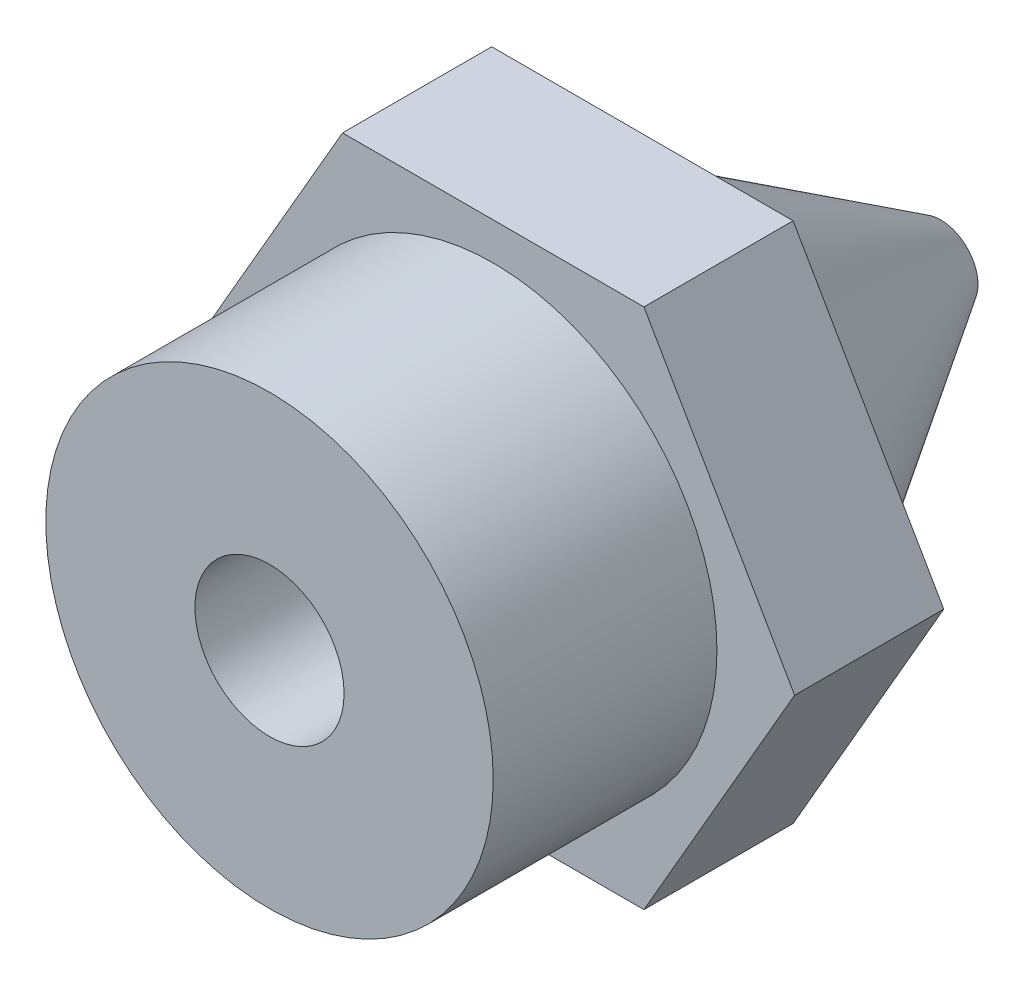
SolidWorks part; units mm, degrees
ref_plane "Plan de face" through (0, 0, 0) normal (0, 0, 1) x (1, 0, 0)
ref_plane "Plan de dessus" through (0, 0, 0) normal (0, 1, 0) x (1, 0, 0)
ref_plane "Plan de droite" through (0, 0, 0) normal (1, 0, 0) x (0, 0, -1)
sketch "Esquisse1" plane through (0, 0, 0) normal (0, 0, 1) x (1, 0, 0)
  line L1 (4.0415, 0) -> (2.0207, 3.5)
  line L2 (2.0207, 3.5) -> (-2.0207, 3.5)
  line L3 (-2.0207, 3.5) -> (-4.0415, 0)
  line L4 (-4.0415, 0) -> (-2.0207, -3.5)
  line L5 (-2.0207, -3.5) -> (2.0207, -3.5)
  line L6 (2.0207, -3.5) -> (4.0415, 0)
  circle A0 centre (0, 0) radius 3.5 construction
  dimension "D1" = 7
extrude "Boss.-Extru.1" add sketch "Esquisse1" along normal blind 9
sketch "Esquisse2" plane through (0, 0, 9) normal (0, 0, 1) x (1, 0, 0)
  line L1 (-7.9912, 5.5023) -> (7.566, 5.5023)
  line L2 (-7.9912, 5.5023) -> (-7.9912, -5.9665)
  line L3 (-7.9912, -5.9665) -> (7.566, -5.9665)
  line L4 (7.566, 5.5023) -> (7.566, -5.9665)
  circle A0 centre (0, 0) radius 3
  dimension "D1" = 6
extrude "Enlèv. mat.-Extru.1" cut sketch "Esquisse2" against normal blind 3
cosmetic thread "Représentation de filetage1" parameters "D2"=4.891
hole_wizard "Diamètre du perçage Ø2.0 (2)1" positions "Esquisse5" profile "Esquisse6" hole size "Ø2.0" standard "ISO"
sketch "Esquisse5" plane through (0, 0, 9) normal (0, 0, 1) x (1, 0, 0)
  point P0 (0, 0)
sketch "Esquisse6" plane through (0, 0, 9) normal (1, 0, 0) x (0, -1, 0)
  line L0 (0, 0) -> (0, 8.1009)
  line L1 (0, 8.1009) -> (1, 7.5)
  line L2 (1, 7.5) -> (1, 0)
  line L5 (1, 0) -> (0, 0)
  line L10 (0, 8.1009) -> (-1, 7.5) construction
  line L11 (0, -6.35) -> (0, 107.95) construction
  dimension "Diamètre du perçage" = 2
  dimension "Profondeur du perçage" = 7.5
  dimension "Angle de pointe" = 118
hole_wizard "Diamètre du perçage Ø1.5 (1.5)1" positions "Esquisse8" profile "Esquisse7" hole size "Ø1.5" standard "ISO"
sketch "Esquisse8" plane through (0, 0, 9) normal (0, 0, 1) x (1, 0, 0)
  point P0 (0, 0)
sketch "Esquisse7" plane through (0, 0, 9) normal (1, 0, 0) x (0, -1, 0)
  line L0 (0, 0) -> (0, 8.6506)
  line L1 (0, 8.6506) -> (0.75, 8.2)
  line L2 (0.75, 8.2) -> (0.75, 0)
  line L5 (0.75, 0) -> (0, 0)
  line L10 (0, 8.6506) -> (-0.75, 8.2) construction
  line L11 (0, -6.35) -> (0, 107.95) construction
  dimension "Diamètre du perçage" = 1.5
  dimension "Profondeur du perçage" = 8.2
  dimension "Angle de pointe" = 118
hole_wizard "Diamètre du perçage Ø0.4 (0.4)1" positions "Esquisse10" profile "Esquisse9" hole size "Ø0.4" standard "ISO"
sketch "Esquisse10" plane through (0, 0, 0) normal (0, 0, -1) x (-1, 0, 0)
  point P0 (0, 0)
sketch "Esquisse9" plane through (0, 0, 0) normal (1, 0, 0) x (0, 1, 0)
  line L0 (0, 0) -> (0, 0.8202)
  line L1 (0, 0.8202) -> (0.2, 0.7)
  line L2 (0.2, 0.7) -> (0.2, 0)
  line L5 (0.2, 0) -> (0, 0)
  line L10 (0, 0.8202) -> (-0.2, 0.7) construction
  line L11 (0, -6.35) -> (0, 107.95) construction
  dimension "Diamètre du perçage" = 0.4
  dimension "Profondeur du perçage" = 0.7
  dimension "Angle de pointe" = 118
sketch "Esquisse3" plane through (0, 0, 0) normal (0, 0, -1) x (-1, 0, 0)
  line L1 (7.8656, -6.0768) -> (-7.4574, -6.0768)
  line L2 (7.8656, -6.0768) -> (7.8656, 5.7844)
  line L3 (7.8656, 5.7844) -> (-7.4574, 5.7844)
  line L4 (-7.4574, -6.0768) -> (-7.4574, 5.7844)
  circle A0 centre (0, 0) radius 3
  dimension "D1" = 6
extrude "Enlèv. mat.-Extru.3" cut sketch "Esquisse3" against normal blind 4
chamfer "Chanfrein2" distance 4 angle 32 1 edges at (-3, 0, 0) first distance on face at (-3, 0, 4)
sketch "Esquisse11" [suppressed] plane through (0, 0, 0) normal (0, 1, 0) x (1, 0, 0)
  line L0 (0, 0) -> (0.5, 0)
  line L1 (3, 0) -> (-3, 0) construction
  line L2 (0, 0) -> (0, -9) construction
  line L3 (-3, -9) -> (3, -9) construction
  line L4 (0, -4) -> (3, -4) construction
  line L5 (2.0207, -4) -> (-2.0207, -4) construction
